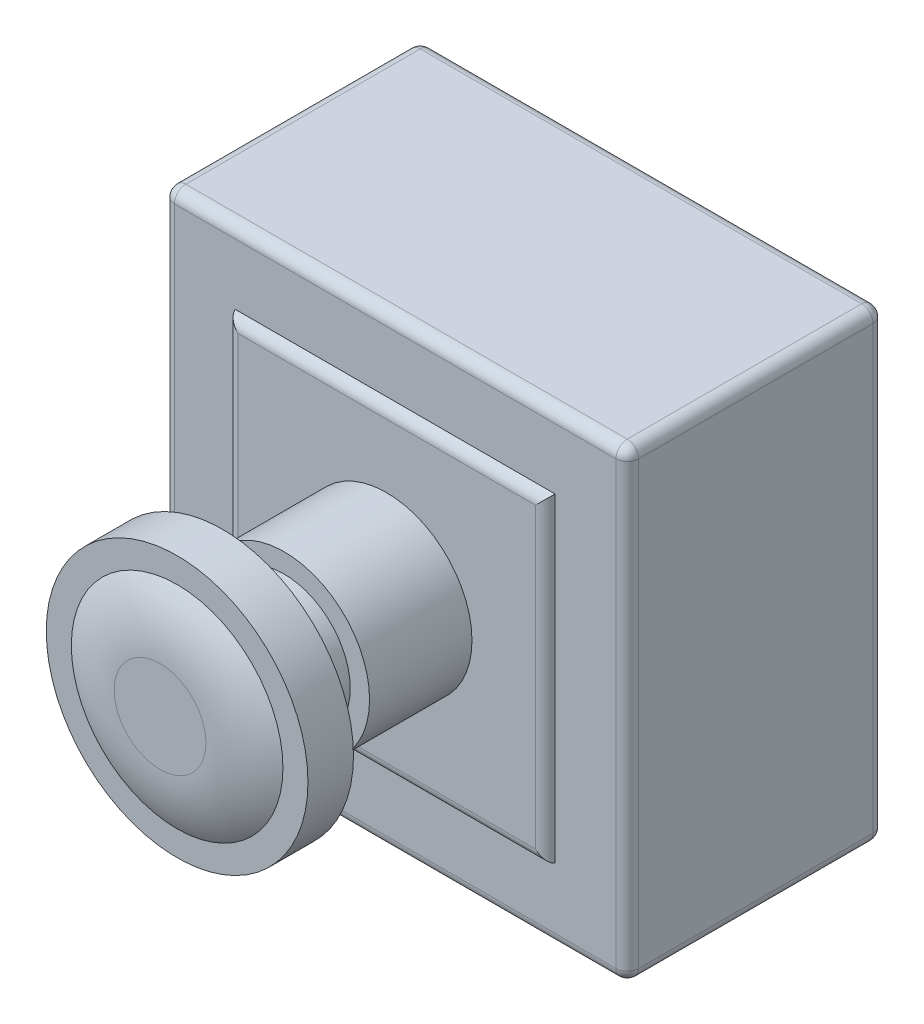
SolidWorks part; units mm, degrees
ref_plane "Alzado" through (0, 0, 0) normal (0, 0, 1) x (1, 0, 0)
ref_plane "Planta" through (0, 0, 0) normal (0, 1, 0) x (1, 0, 0)
ref_plane "Vista lateral" through (0, 0, 0) normal (1, 0, 0) x (0, 0, -1)
sketch "Croquis1" plane through (0, 0, 0) normal (0, 0, 1) x (1, 0, 0)
  line L1 (-20.4, 20.4) -> (20.4, 20.4)
  line L2 (-20.4, 20.4) -> (-20.4, -20.4)
  line L3 (-20.4, -20.4) -> (20.4, -20.4)
  line L4 (20.4, 20.4) -> (20.4, -20.4)
  line L5 (-20.4, 20.4) -> (20.4, -20.4) construction
  line L6 (-20.4, -20.4) -> (20.4, 20.4) construction
  point P0 (0, 0)
  dimension "D1" = 40.8
extrude "Saliente-Extruir1" add sketch "Croquis1" along normal mid plane 22.6
sketch "Croquis2" plane through (0, 0, 11.3) normal (0, 0, 1) x (1, 0, 0)
  line L1 (-14.05, 14.05) -> (14.05, 14.05)
  line L2 (-14.05, 14.05) -> (-14.05, -14.05)
  line L3 (-14.05, -14.05) -> (14.05, -14.05)
  line L4 (14.05, 14.05) -> (14.05, -14.05)
  line L5 (-14.05, 14.05) -> (14.05, -14.05) construction
  line L6 (-14.05, -14.05) -> (14.05, 14.05) construction
  point P0 (0, 0)
  dimension "D1" = 28.1
extrude "Saliente-Extruir2" add sketch "Croquis2" along normal mid plane 1.5
fillet "Redondeo1" radius 1 4 edges at (14.05, 0, 12.05) (0, 14.05, 12.05) (0, -14.05, 12.05) (-14.05, 0, 12.05)
sketch "Croquis3" plane through (0, 0, 12.05) normal (0, 0, 1) x (1, 0, 0)
  circle A0 centre (0, 0) radius 7.5
  dimension "D1" = 15
extrude "Saliente-Extruir3" add sketch "Croquis3" along normal blind 9
sketch "Croquis4" plane through (0, 0, 21.05) normal (0, 0, 1) x (1, 0, 0)
  circle A2 centre (0, 0) radius 5.8
  circle A3 centre (0, 0) radius 5.8
  dimension "D1" = 1.7
extrude "Saliente-Extruir4" add sketch "Croquis4" along normal blind 7
sketch "Croquis5" plane through (0, 0, 28.05) normal (0, 0, 1) x (1, 0, 0)
  circle A0 centre (-0.4142, 0) radius 11.5
  dimension "D1" = 23
extrude "Saliente-Extruir5" add sketch "Croquis5" along normal mid plane 4
sketch "Croquis6" plane through (0, 0, 30.05) normal (0, 0, 1) x (1, 0, 0)
  circle A2 centre (-0.4142, 0) radius 9.3
  circle A3 centre (-0.4142, 0) radius 9.3
  dimension "D1" = 2.2
extrude "Saliente-Extruir6" add sketch "Croquis6" along normal mid plane 3
fillet "Redondeo4" radius 10 1 edges at (8.8858, 0, 31.55)
sketch "Croquis7" plane through (0, 0, -11.3) normal (0, 0, -1) x (-1, 0, 0)
  line L0 (-20.4, 20.4) -> (20.4, 20.4) construction
  line L1 (-20.4, -20.4) -> (-20.4, 20.4) construction
  circle A0 centre (-9.4, 11.9) radius 2.5
  dimension "D1" = 8.5
  dimension "D2" = 11
  dimension "D3" = 5
extrude "Saliente-Extruir7" add sketch "Croquis7" along normal blind 5
fillet "Redondeo5" radius 1 12 edges at (0, -20.4, 11.3) (-20.4, 0, 11.3) (0, 20.4, 11.3) (20.4, 0, 11.3) (-20.4, 0, -11.3) (0, 20.4, -11.3) (20.4, 0, -11.3) (0, -20.4, -11.3) (-20.4, -20.4, 0) (20.4, -20.4, 0) (20.4, 20.4, 0) (-20.4, 20.4, 0)
